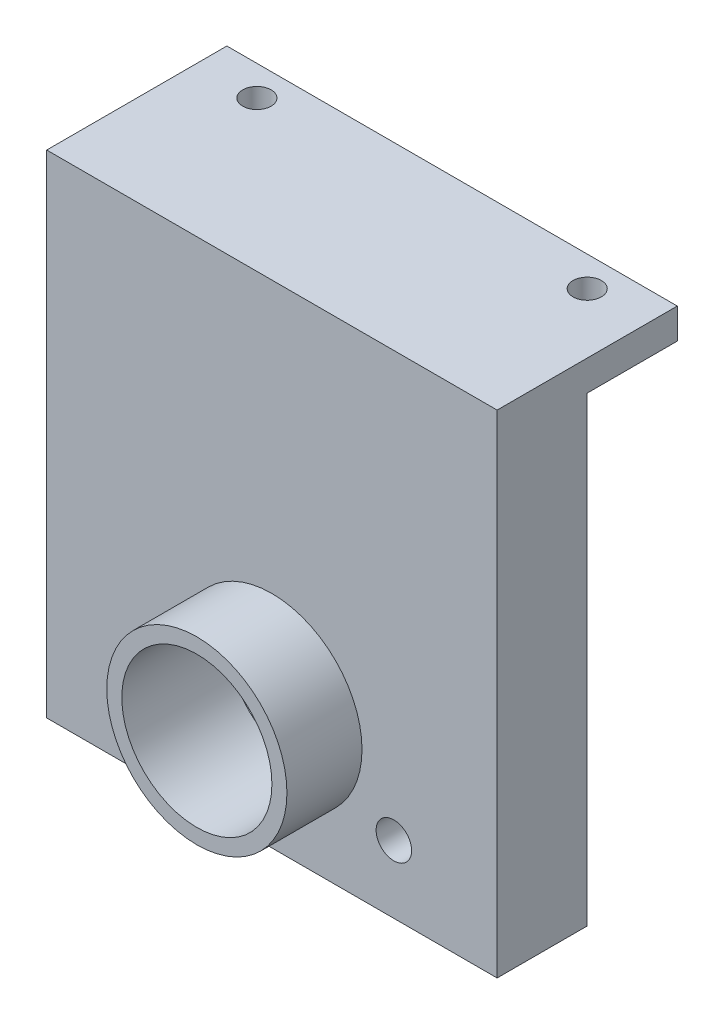
SolidWorks part; units mm, degrees
ref_plane "Front Plane" through (0, 0, 0) normal (0, 0, 1) x (1, 0, 0)
ref_plane "Top Plane" through (0, 0, 0) normal (0, 1, 0) x (1, 0, 0)
ref_plane "Right Plane" through (0, 0, 0) normal (1, 0, 0) x (0, 0, -1)
sketch "Sketch2" plane through (0, 0, 0) normal (0, 0, 1) x (1, 0, 0)
  line L6 (-16.51, 36.5252) -> (-16.51, 2.54)
  line L7 (-16.51, 2.54) -> (16.51, 2.54)
  line L8 (16.51, 2.54) -> (16.51, 36.5252)
  line L9 (19.05, 41.6052) -> (19.05, 0)
  line L10 (-19.05, 0) -> (19.05, 0)
  line L11 (-19.05, 41.6052) -> (-19.05, 0)
  line L13 (-19.05, 41.6052) -> (19.05, 41.6052)
  line L14 (-16.51, 36.5252) -> (16.51, 36.5252)
extrude "Boss-Extrude1" add sketch "Sketch2" along normal blind 5.08
sketch "Sketch4" plane through (0, 0, 0) normal (0, 0, -1) x (-1, 0, 0)
  line L0 (-19.05, 41.6052) -> (19.05, 41.6052) construction
  line L1 (-19.05, 41.6052) -> (19.05, 41.6052)
  line L2 (-19.05, 41.6052) -> (-19.05, 39.0362)
  line L3 (-19.05, 0) -> (-19.05, 41.6052) construction
  line L4 (-19.05, 39.0362) -> (19.05, 39.0652)
  line L5 (19.05, 41.6052) -> (19.05, 0) construction
  line L7 (19.05, 39.0652) -> (19.05, 41.6052)
extrude "Boss-Extrude2" add sketch "Sketch4" along normal blind 7.62
hole_wizard "M2 Clearance Hole1" positions "Sketch5" profile "Sketch6" hole size "M2" standard "ANSI Metric" end condition through all
sketch "Sketch5" plane through (0, 41.6052, 0) normal (0, 1, 0) x (1, 0, 0)
  line L0 (19.05, 0) -> (-19.05, 0) construction
  line L1 (19.05, -5.08) -> (19.05, 7.62) construction
  line L2 (-19.05, -5.08) -> (-19.05, 7.62) construction
  line L4 (-13.97, 5.08) -> (13.97, 5.08) construction
  point P0 (-13.97, 5.08)
  point P2 (13.97, 5.08)
  point P18 (0, 5.08)
  point P19 (0, 0)
  dimension "D1" = 5.08
  dimension "D2" = 5.08
sketch "Sketch6" plane through (-13.97, 41.6052, -5.08) normal (1, 0, 0) x (0, 0, 1)
  line L0 (0, 0) -> (0, 41.6052)
  line L1 (0, 41.6052) -> (1.2, 41.6052)
  line L2 (1.2, 41.6052) -> (1.2, 0)
  line L5 (1.2, 0) -> (0, 0)
  line L11 (0, -6.35) -> (0, 107.95) construction
  dimension "Thru Hole Dia." = 2.4
  dimension "Thru Hole Depth" = 41.6052
sketch "Sketch7" plane through (0, 0, 5.08) normal (0, 0, 1) x (1, 0, 0)
  line L12 (-10.3149, 5.715) -> (10.3149, 5.715) construction
  line L13 (-19.05, 0) -> (19.05, 0) construction
  circle A0 centre (-10.3149, 5.715) radius 1.5011
  circle A1 centre (10.3149, 5.715) radius 1.5011
  point P13 (0, 5.715)
  dimension "D1" = 3.0023
  dimension "D3" = 20.6299
  dimension "D2" = 5.715
sketch "Sketch8" plane through (0, 0, 5.08) normal (0, 0, 1) x (1, 0, 0)
  line L1 (0, 11.0261) -> (0, 0) construction
  line L2 (-16.51, 4.6761) -> (16.51, 4.6761) construction
  line L3 (-16.51, 36.5252) -> (-16.51, 2.54) construction
  line L4 (16.51, 2.54) -> (16.51, 36.5252) construction
  line L5 (-19.05, 0) -> (19.05, 0) construction
  line L6 (19.05, 0) -> (19.05, 41.6052) construction
  line L7 (19.05, 41.6052) -> (-19.05, 41.6052) construction
  line L8 (-19.05, 41.6052) -> (-19.05, 0) construction
  line L9 (-19.05, 0) -> (19.05, 0)
  line L10 (19.05, 0) -> (19.05, 41.6052)
  line L11 (19.05, 41.6052) -> (-19.05, 41.6052)
  line L12 (-19.05, 41.6052) -> (-19.05, 0)
  circle A0 centre (0, 11.0261) radius 6.35
  dimension "D1" = 12.7
  dimension "D2" = 11.0261
extrude "Boss-Extrude3" add sketch "Sketch8" along normal blind 2.54
extrude "Cut-Extrude1" cut sketch "Sketch7" against normal through all both and the other way through all
sketch "Sketch9" plane through (0, 0, 7.62) normal (0, 0, 1) x (1, 0, 0)
  circle A1 centre (0, 11.0261) radius 6.35 construction
  circle A2 centre (0, 11.0261) radius 7.62
  circle A3 centre (0, 11.0261) radius 7.62
  circle A4 centre (0, 11.0261) radius 6.35
  dimension "D1" = 1.27
extrude "Boss-Extrude4" add sketch "Sketch9" along normal blind 6.35
equation "\"D1@Sketch7\"=2*0.0591in"
